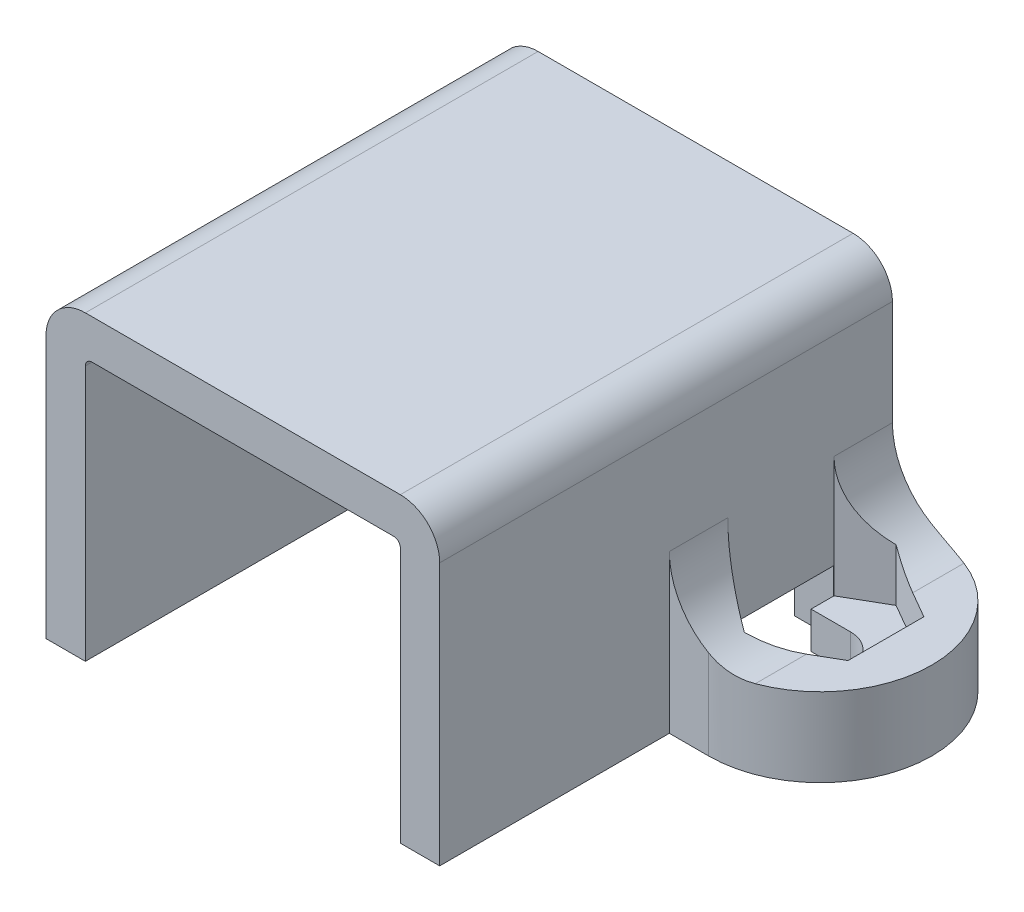
SolidWorks part; units mm, degrees
ref_plane "Front Plane" through (0, 0, 0) normal (0, 0, 1) x (1, 0, 0)
ref_plane "Top Plane" through (0, 0, 0) normal (0, 1, 0) x (1, 0, 0)
ref_plane "Right Plane" through (0, 0, 0) normal (1, 0, 0) x (0, 0, -1)
sketch "Sketch1" plane through (0, 0, 0) normal (0, 0, 1) x (1, 0, 0)
  line L0 (0, 0) -> (0, 11.5)
  line L1 (0, 11.5) -> (15, 11.5)
  line L2 (15, 11.5) -> (15, 0)
  line L3 (15, 0) -> (13.5, 0)
  line L4 (13.5, 0) -> (13.5, 10)
  line L5 (13.5, 10) -> (1.5, 10)
  line L6 (1.5, 10) -> (1.5, 0)
  line L7 (1.5, 0) -> (0, 0)
  dimension "D1" = 15
  dimension "D2" = 11.5
  dimension "D3" = 1.5
  dimension "D4" = 1.5
  dimension "D5" = 1.5
extrude "Boss-Extrude1" add sketch "Sketch1" along normal blind 17.25
fillet "Fillet1" radius 1.5 2 edges at (0, 11.5, 8.625) (15, 11.5, 8.625)
sketch "Sketch2" plane through (0, 0, 0) normal (0, -1, 0) x (1, 0, 0)
  line L0 (0, 0) -> (0, 8.5)
  line L1 (0, 17.25) -> (0, 0) construction
  line L2 (0, 8.5) -> (-1.5, 8.5)
  line L3 (0, 0) -> (-1.5, 0)
  line L4 (7.5, 0) -> (7.5, 18.3689) construction
  line L5 (1.5, 0) -> (13.5, 0) construction
  line L6 (15, 0) -> (16.5, 0)
  line L7 (15, 8.5) -> (16.5, 8.5)
  line L8 (15, 0) -> (15, 8.5)
  arc A0 (-1.5, 0) -> (-1.5, 8.5) centre (-1.5, 4.25) cw
  arc A1 (16.5, 0) -> (16.5, 8.5) centre (16.5, 4.25) ccw
  dimension "D1" = 8.5
  dimension "D2" = 18
extrude "Boss-Extrude2" add sketch "Sketch2" against normal blind 3
fillet "Fillet2" radius 0.25 2 edges at (1.5, 10, 8.625) (13.5, 10, 8.625)
sketch "Sketch3" plane through (0, 0, 0) normal (0, -1, 0) x (1, 0, 0)
  line L0 (13.5, 2.24) -> (13.5, 6.27)
  line L1 (13.5, 17.25) -> (13.5, 0) construction
  line L2 (13.5, 0) -> (16.5, 0) construction
  line L3 (13.5, 2.24) -> (15, 2.24)
  line L4 (15, 2.24) -> (15, 3.1)
  line L5 (15, 6.27) -> (13.5, 6.27)
  line L6 (15, 5.41) -> (16.5, 5.41)
  line L7 (15, 3.1) -> (16.5, 3.1)
  line L8 (15, 5.41) -> (15, 6.27)
  line L9 (7.5, 17.25) -> (7.5, -5.5563) construction
  line L10 (1.75, 17.25) -> (13.25, 17.25) construction
  line L11 (0, 5.41) -> (0, 6.27)
  line L12 (0, 3.1) -> (-1.5, 3.1)
  line L13 (0, 5.41) -> (-1.5, 5.41)
  line L14 (0, 6.27) -> (1.5, 6.27)
  line L15 (0, 2.24) -> (0, 3.1)
  line L16 (1.5, 2.24) -> (0, 2.24)
  line L17 (1.5, 2.24) -> (1.5, 6.27)
  line L18 (13.5, 17.25) -> (13.5, 0) construction
  line L19 (1.5, 17.25) -> (1.5, 0) construction
  arc A0 (16.5, 5.41) -> (16.5, 3.1) centre (16.5, 4.255) cw
  arc A1 (-1.5, 5.41) -> (-1.5, 3.1) centre (-1.5, 4.255) ccw
  dimension "D1" = 2.24
  dimension "D2" = 4.03
  dimension "D3" = 1.5
  dimension "D4" = 0.86
  dimension "D5" = 0.86
  dimension "D6" = 1.5
  dimension "D7" = 1.5
extrude "Cut-Extrude5" cut sketch "Sketch3" against normal blind 1.4
sketch "Sketch4" plane through (0, 1.4, 0) normal (0, -1, 0) x (1, 0, 0)
  line L0 (1.5, 2.24) -> (1.5, 6.27)
  line L1 (1.5, 6.27) -> (0, 6.27)
  line L2 (0, 6.27) -> (0, 2.24)
  line L3 (7.5, 0) -> (7.5, 17.25) construction
  line L4 (1.75, 0) -> (13.25, 0) construction
  line L5 (1.75, 17.25) -> (13.25, 17.25) construction
  line L6 (0, 2.24) -> (1.5, 2.24)
  line L7 (15, 2.24) -> (13.5, 2.24)
  line L8 (15, 6.27) -> (15, 2.24)
  line L9 (13.5, 6.27) -> (15, 6.27)
  line L10 (13.5, 2.24) -> (13.5, 6.27)
extrude "Cut-Extrude7" cut sketch "Sketch4" against normal blind 1
sketch "Sketch5" plane through (0, 3, 0) normal (0, 1, 0) x (1, 0, 0)
  line L0 (-1.5, -1.36) -> (-1.5, -7.2434) construction
  line L1 (-1.5, -1.36) -> (-4.0028, -2.805)
  line L2 (-4.0028, -2.805) -> (-4.0028, -5.695)
  line L3 (-4.0028, -5.695) -> (-1.5, -7.14)
  line L4 (-1.5, -7.14) -> (0, -6.274)
  line L6 (0, -2.226) -> (-1.5, -1.36)
  line L7 (0, -2.226) -> (0, -6.274)
  line L8 (0, 0) -> (0, -8.5) construction
  line L9 (7.5, 0) -> (7.5, -17.25) construction
  line L10 (1.0028, -5.695) -> (1.0028, -4.25) [skipped]
  line L11 (13.5, 0) -> (1.5, 0) construction
  line L12 (13.5, -17.25) -> (1.5, -17.25) construction
  line L13 (16.5, -1.36) -> (16.5, -7.2434) construction
  line L14 (15, -2.226) -> (15, -6.274)
  line L15 (15, -2.226) -> (16.5, -1.36)
  line L16 (16.5, -7.14) -> (15, -6.274)
  line L17 (19.0028, -5.695) -> (16.5, -7.14)
  line L18 (19.0028, -2.805) -> (19.0028, -5.695)
  line L19 (16.5, -1.36) -> (19.0028, -2.805)
  circle A0 centre (-1.5, -4.25) radius 2.5028 construction
  circle A1 centre (16.5, -4.25) radius 2.5028 construction
  dimension "D1" = 2.89
extrude "Cut-Extrude9" cut sketch "Sketch5" against normal blind 1.6
fillet "Fillet4" radius 3 4 edges at (15, 3, 1.113) (15, 3, 7.387) (0, 3, 1.113) (0, 3, 7.387)
